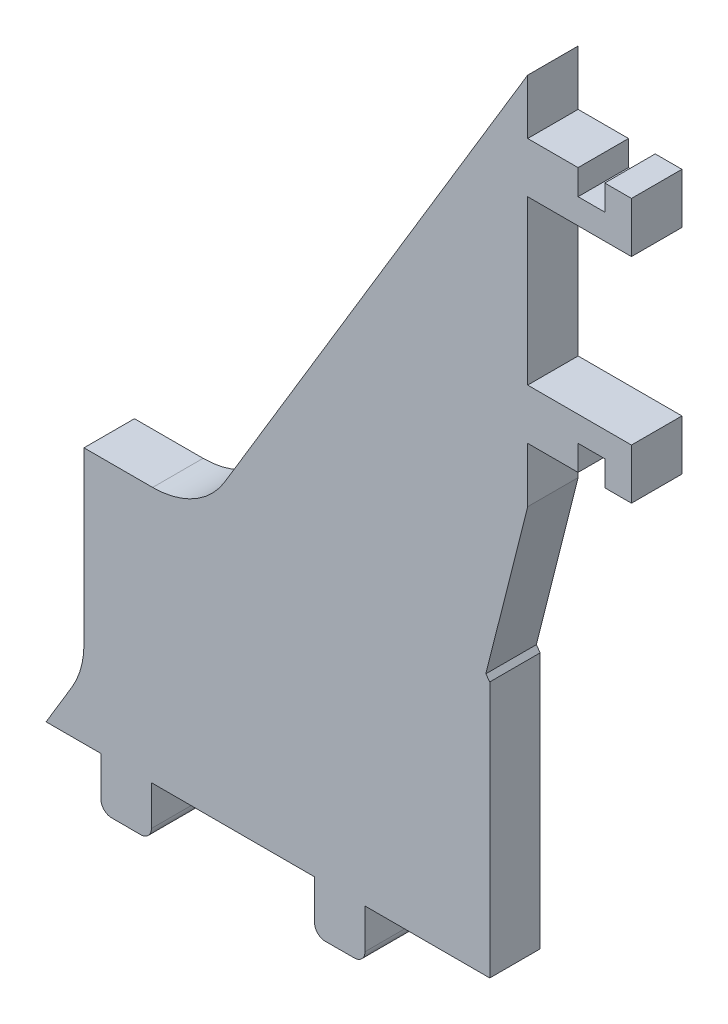
SolidWorks part; units mm, degrees
ref_plane "Front Plane" through (0, 0, 0) normal (0, 0, 1) x (1, 0, 0)
ref_plane "Top Plane" through (0, 0, 0) normal (0, 1, 0) x (1, 0, 0)
ref_plane "Right Plane" through (0, 0, 0) normal (1, 0, 0) x (0, 0, -1)
sketch "Sketch1" plane through (0, 0, 0) normal (0, 0, 1) x (1, 0, 0)
  line L0 (28.6385, 47.625) -> (28.6385, 41.0972)
  line L1 (28.6385, 3.175) -> (15.8115, -47.625)
  line L2 (15.8115, -47.625) -> (9.2837, -47.625)
  line L3 (-28.6385, -47.625) -> (28.6385, 47.625)
  line L4 (28.6385, 35.1028) -> (40.9829, 35.1028)
  line L5 (40.9829, 35.1028) -> (40.9829, 41.0972)
  line L6 (40.9829, 41.0972) -> (37.8079, 41.0972)
  line L7 (37.8079, 41.0972) -> (37.8079, 38.1)
  line L8 (37.8079, 38.1) -> (34.6329, 38.1)
  line L9 (34.6329, 38.1) -> (34.6329, 41.0972)
  line L10 (34.6329, 41.0972) -> (28.6385, 41.0972)
  line L11 (28.6385, 25.4) -> (93.7621, 25.4) construction
  line L12 (34.6329, 9.7028) -> (28.6385, 9.7028)
  line L13 (34.6329, 12.7) -> (34.6329, 9.7028)
  line L14 (37.8079, 12.7) -> (34.6329, 12.7)
  line L15 (37.8079, 9.7028) -> (37.8079, 12.7)
  line L16 (40.9829, 9.7028) -> (37.8079, 9.7028)
  line L17 (40.9829, 15.6972) -> (40.9829, 9.7028)
  line L18 (28.6385, 15.6972) -> (40.9829, 15.6972)
  line L19 (-6.4135, -47.625) -> (-6.4135, -79.0493) construction
  line L20 (-22.1107, -47.625) -> (-22.1107, -53.6194)
  line L21 (-22.1107, -53.6194) -> (-19.1135, -53.6194)
  line L22 (-19.1135, -53.6194) -> (-19.1135, -56.7944)
  line L23 (-19.1135, -56.7944) -> (-22.1107, -56.7944)
  line L24 (-22.1107, -56.7944) -> (-22.1107, -59.9694)
  line L25 (-22.1107, -59.9694) -> (-16.1163, -59.9694)
  line L26 (-16.1163, -59.9694) -> (-16.1163, -47.625)
  line L27 (3.2893, -59.9694) -> (3.2893, -47.625)
  line L28 (9.2837, -59.9694) -> (3.2893, -59.9694)
  line L29 (9.2837, -56.7944) -> (9.2837, -59.9694)
  line L30 (6.2865, -56.7944) -> (9.2837, -56.7944)
  line L31 (6.2865, -53.6194) -> (6.2865, -56.7944)
  line L32 (9.2837, -53.6194) -> (6.2865, -53.6194)
  line L33 (9.2837, -47.625) -> (9.2837, -53.6194)
  line L34 (-22.1107, -47.625) -> (-28.6385, -47.625)
  line L35 (3.2893, -47.625) -> (-16.1163, -47.625)
  line L36 (28.6385, 9.7028) -> (28.6385, 3.175)
  line L37 (28.6385, 35.1028) -> (28.6385, 15.6972)
  point P2 (0, 0)
  dimension "D1" = 44.45
  dimension "D2" = 5.9944
  dimension "D3" = 3.175
  dimension "D4" = 3.175
  dimension "D5" = 5.9944
  dimension "D6" = 2.9972
  dimension "D7" = 25.4
  dimension "D8" = 57.3278
  dimension "D9" = 5.9944
  dimension "D10" = 3.175
  dimension "D11" = 3.175
  dimension "D12" = 2.9972
  dimension "D13" = 5.9944
  dimension "D14" = 25.4
  dimension "D15" = 19.3548
  dimension "D16" = 44.45
extrude "Boss-Extrude1" add sketch "Sketch1" along normal blind 6
sketch "Sketch2" plane through (0, 0, 6) normal (0, 0, 1) x (1, 0, 0)
  line L0 (28.6385, 24.2131) -> (-14.5601, -47.625) construction
  line L1 (28.6385, 15.6972) -> (28.6385, 35.1028) construction
  line L2 (-16.1163, -47.625) -> (3.2893, -47.625) construction
  line L3 (28.6385, 47.625) -> (-28.6385, -47.625) construction
  line L4 (14.1896, 6.001) -> (7.8412, -4.5563)
  line L5 (7.8412, -4.5563) -> (12.9783, -7.6454)
  line L6 (12.9783, -7.6454) -> (19.3267, 2.9118)
  line L7 (19.3267, 2.9118) -> (14.1896, 6.001)
  line L8 (7.8412, -4.5563) -> (19.3267, 2.9118) construction
  line L9 (14.1896, 6.001) -> (12.9783, -7.6454) construction
  line L10 (1.1001, -15.7665) -> (6.2372, -18.8557)
  line L11 (6.2372, -18.8557) -> (-0.1112, -29.4129)
  line L12 (-0.1112, -29.4129) -> (-5.2484, -26.3238)
  line L13 (-5.2484, -26.3238) -> (1.1001, -15.7665)
  line L15 (7.8412, -4.5563) -> (1.1001, -15.7665) construction
  line L16 (7.0392, -11.706) -> (4.4706, -10.1614) construction
  point P8 (13.5839, -0.8222)
  dimension "D1" = 5.9944
  dimension "D2" = 12.319
  dimension "D3" = 12.065
  dimension "D4" = 12.319
  dimension "D5" = 5.9944
  dimension "D6" = 13.081
sketch "Sketch3" plane through (0, 0, 6) normal (0, 0, 1) x (1, 0, 0)
  line L0 (-16.1163, -47.625) -> (3.2893, -47.625) construction
  line L1 (-24.13, -17.145) -> (24.13, -17.145)
  line L2 (-24.13, -17.145) -> (-24.13, -47.625)
  line L3 (-24.13, -47.625) -> (24.13, -47.625)
  line L4 (24.13, -17.145) -> (24.13, -47.625)
  line L5 (28.6385, 25.4) -> (-28.6385, 25.4) construction
  line L6 (28.6385, 15.6972) -> (28.6385, 35.1028) construction
  line L7 (-28.6385, 25.4) -> (-28.6385, -47.625) construction
  line L8 (-28.6385, -47.625) -> (-22.1107, -47.625) construction
  line L9 (28.6385, 47.625) -> (-28.6385, -47.625) construction
  line L10 (0, 25.4) -> (0, -17.145) construction
  dimension "D1" = 30.48
  dimension "D2" = 48.26
extrude "Boss-Extrude2" add sketch "Sketch3" against normal up to surface (6 mm away) contours L1 L4 L3 L2 up to face at (14.169, -14.169, 0)
chamfer "Chamfer1" distance 0.635 1 edges at (23.5077, -17.145, 3)
fillet "Fillet1" radius 10 2 edges at (-24.13, -40.1275, 3) (-10.3099, -17.145, 3)
sketch "Sketch4" plane through (0, 0, 6) normal (0, 0, 1) x (1, 0, 0)
  line L0 (-22.1107, -47.625) -> (-22.1107, -53.6194) construction
  line L1 (-22.1107, -53.625) -> (9.2837, -53.625)
  line L2 (-22.1107, -53.625) -> (-22.1107, -59.9694)
  line L3 (-22.1107, -59.9694) -> (9.2837, -59.9694)
  line L4 (9.2837, -53.625) -> (9.2837, -59.9694)
  line L5 (-28.6385, -47.625) -> (-22.1107, -47.625) construction
  dimension "D1" = 6
extrude "Cut-Extrude1" cut sketch "Sketch4" against normal through all
fillet "Fillet2" radius 1.27 4 edges at (9.2837, -53.6194, 3) (3.2893, -53.625, 3) (-16.1163, -53.625, 3) (-22.1107, -53.6194, 3)
